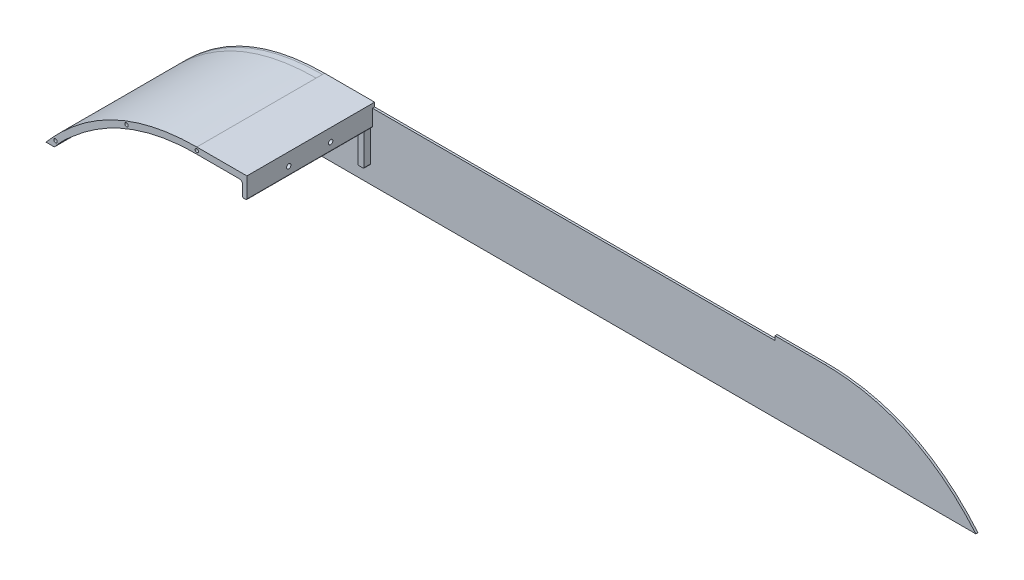
SolidWorks part; units mm, degrees
ref_plane "Front Plane" through (0, 0, 0) normal (0, 0, 1) x (1, 0, 0)
ref_plane "Top Plane" through (0, 0, 0) normal (0, 1, 0) x (1, 0, 0)
ref_plane "Right Plane" through (0, 0, 0) normal (1, 0, 0) x (0, 0, -1)
sketch "Sketch1" plane through (0, 0, 0) normal (0, 0, 1) x (1, 0, 0)
  line L0 (0, 0) -> (-304.8, 0)
  line L1 (0, 0) -> (609.6, 0)
  line L2 (0, 0) -> (0, 107.95) construction
  line L3 (0, 107.95) -> (609.6, 107.95)
  line L4 (609.6, 0) -> (609.6, 107.95) construction
  line L5 (609.6, 0) -> (914.4, 0)
  line L6 (304.8, -1000) -> (304.8, 49000) construction
  line L7 (0, 107.95) -> (-76.2, 107.95)
  line L8 (609.6, 107.95) -> (685.8, 107.95)
  spline S0 degree 2 poles (-304.8, 0) (-213.404, 107.36) (-76.2, 107.95) knots 0 0 0 1 1 1
  spline S1 degree 2 poles (914.4, 0) (823.004, 107.36) (685.8, 107.95) knots 0 0 0 1 1 1
  point P11 (304.8, 0)
  dimension "D1" = 609.6
  dimension "D2" = 107.95
  dimension "D3" = 304.8
  dimension "D4" = 76.2
extrude "Boss-Extrude1" add sketch "Sketch1" along normal blind 3.175
sketch "Sketch2" plane through (0, 0, 3.175) normal (0, 0, 1) x (1, 0, 0)
  line L8 (685.8, 107.95) -> (-76.2, 107.95) construction
  line L11 (0, 107.95) -> (609.6, 107.95)
  line L12 (0, 107.95) -> (0, 101.6) construction
  line L13 (0, 101.6) -> (609.6, 101.6)
  line L14 (609.6, 107.95) -> (609.6, 101.6) construction
  line L15 (-0.254, 107.95) -> (-0.254, 101.6)
  line L16 (609.854, 107.95) -> (609.854, 101.6)
  line L19 (609.6, 107.95) -> (609.854, 107.95)
  line L20 (609.6, 101.6) -> (609.854, 101.6)
  line L21 (-0.254, 107.95) -> (0, 107.95)
  line L22 (-0.254, 101.6) -> (0, 101.6)
  dimension "D1" = 609.6
  dimension "D2" = 6.35
  dimension "D3" = 0.254
  dimension "D4" = 0.254
extrude "Cut-Extrude1" cut sketch "Sketch2" against normal through all
sketch "Sketch3" plane through (0, 0, 3.175) normal (0, 0, 1) x (1, 0, 0)
  line L5 (-76.0908, 82.5502) -> (-76.2, 107.95) construction
  line L6 (685.8, 107.95) -> (609.854, 107.95)
  line L7 (609.854, 107.95) -> (609.854, 101.6)
  line L8 (609.854, 101.6) -> (-0.254, 101.6)
  line L9 (-0.254, 101.6) -> (-0.254, 107.95)
  line L10 (-0.254, 107.95) -> (-76.2, 107.95)
  line L11 (-304.8, 0) -> (914.4, 0)
  line L19 (-304.8, 0) -> (-254.508, 0)
  line L20 (-304.8, 0) -> (914.4, 0) construction
  line L21 (-254.508, 0) -> (-254.508, 15.3448)
  line L22 (-76.2, 107.95) -> (-0.254, 107.95)
  line L23 (-0.254, 107.95) -> (-0.254, 76.2)
  line L24 (-0.254, 76.2) -> (-6.604, 76.2)
  line L25 (-6.604, 76.2) -> (-6.604, 82.5502)
  line L26 (-6.604, 82.5502) -> (-76.0908, 82.5502)
  parabola Q2 (-76.2, 107.95) -> (-304.8, 0) focus (-138.8032, -41.5009) apex (-192.9562, 84.7198)
  parabola Q3 (914.4, 0) -> (685.8, 107.95) focus (748.4032, -41.5009) apex (802.5562, 84.7198)
  parabola Q4 (-76.2, 107.95) -> (-304.8, 0) focus (-138.8032, -41.5009) apex (-192.9562, 84.7198)
  spline S0 degree 1 poles (-76.0908, 82.5502) (-285.4592, -16.4649) knots 0 0 1 1 construction
  spline S1 degree 3 poles (-76.0908, 82.5502) (-78.7263, 82.5389) (-84.0207, 82.4515) (-94.414, 82.0204) (-107.175, 81.0024) (-122.0857, 79.0209) (-140.2937, 75.5918) (-157.8592, 70.8643) (-175.9104, 64.4537) (-194.5198, 56.4637) (-212.4049, 46.7322) (-228.6865, 35.996) (-240.414, 27.3) (-249.9299, 19.4397) (-257.5609, 12.6326) (-263.3873, 7.1473) (-268.2089, 2.3627) (-271.8925, -1.4301) (-275.5622, -5.3024) (-280.0978, -10.2646) (-283.6939, -14.3913) (-285.4592, -16.4649) knots 0.497516 0.497516 0.497516 0.497516 0.497684 0.497853 0.498189 0.498526 0.498863 0.499456 0.499793 0.50021 0.500884 0.501221 0.501558 0.501878 0.502046 0.502231 0.502399 0.502483 0.502568 0.502737 0.502905 0.502905 0.502905 0.502905 only from (-76.0908, 82.5502) to (-270.5007, 0) construction
  spline S2 degree 2 poles (-254.508, 15.3448) (-177.7983, 82.8932) (-76.0908, 82.5502) knots 0 0 0 1 1 1
  dimension "D2" = 31.75
  dimension "D3" = 6.35
  dimension "D5" = 50.292
  dimension "D1" = 0
  dimension "D4" = 25.4
extrude "Boss-Extrude2" add sketch "Sketch3" along normal blind 9.525
sketch "Sketch5" plane through (0, 0, 12.7) normal (0, 0, 1) x (1, 0, 0)
  line L7 (-304.8, 0) -> (-292.1, 0)
  line L8 (-76.0372, 98.4251) -> (-6.604, 98.4251)
  line L9 (-6.604, 98.4251) -> (-6.604, 82.5502)
  line L14 (-304.8, 0) -> (-254.508, 0)
  line L15 (-254.508, 0) -> (-254.508, 15.3448)
  line L16 (-76.0908, 82.5502) -> (-6.604, 82.5502)
  line L17 (-6.604, 82.5502) -> (-6.604, 76.2)
  line L18 (-6.604, 76.2) -> (-0.254, 76.2)
  line L19 (-0.254, 76.2) -> (-0.254, 107.95)
  line L20 (-0.254, 107.95) -> (-76.2, 107.95)
  line L24 (-6.604, 82.5502) -> (-6.604, 76.2)
  line L25 (-6.604, 76.2) -> (-0.254, 76.2)
  line L26 (-0.254, 76.2) -> (-0.254, 107.95)
  line L27 (-0.254, 107.95) -> (-76.2, 107.95)
  parabola Q4 (-76.2, 107.95) -> (-304.8, 0) focus (-138.8032, -41.5009) apex (-192.9562, 84.7198)
  parabola Q5 (-254.508, 15.3448) -> (-76.0908, 82.5502) focus (-126.3995, -51.2914) apex (-169.7975, 66.5726)
  parabola Q6 (-76.2, 107.95) -> (-304.8, 0) focus (-138.8032, -41.5009) apex (-192.9562, 84.7198)
  parabola Q7 (-254.508, 15.3448) -> (-76.0908, 82.5502) focus (-126.3995, -51.2914) apex (-169.7975, 66.5726) construction
  spline S0 degree 1 poles (-264.9993, 27.259) (-76.0372, 98.4251) knots 0 0 1 1 construction
  spline S1 degree 3 poles (-264.9993, 27.259) (-263.3249, 28.7335) (-259.9376, 31.6547) (-253.107, 37.2998) (-244.419, 44.0244) (-233.7687, 51.5472) (-219.2659, 60.8476) (-200.5783, 71.0931) (-177.2837, 81.1523) (-153.1553, 88.9561) (-132.3866, 93.5719) (-115.3933, 96.1333) (-102.4647, 97.4901) (-91.5371, 98.1519) (-82.7134, 98.4012) (-78.2591, 98.4326) (-76.0372, 98.4251) knots 0.497832 0.497832 0.497832 0.497832 0.497965 0.498098 0.498363 0.498629 0.498895 0.499427 0.499958 0.50049 0.501022 0.501287 0.501553 0.501819 0.501952 0.502085 0.502085 0.502085 0.502085
  spline S2 degree 2 poles (-264.9993, 27.259) (-280.0432, 15.0907) (-292.1, 0) knots 0 0 0 1 1 1
  dimension "D3" = 12.7
  dimension "D1" = 0
  dimension "D2" = 15.875
extrude "Boss-Extrude3" add sketch "Sketch5" along normal blind 180.975
sketch "Sketch6" plane through (0, 0, 12.7) normal (0, 0, 1) x (1, 0, 0)
  line L1 (-254.508, 0) -> (-226.4253, 0)
  line L2 (-254.508, 0) -> (-254.508, 28.575)
  line L3 (-254.508, 28.575) -> (-226.4253, 28.575)
  line L4 (-226.4253, 0) -> (-226.4253, 28.575)
  dimension "D1" = 28.575
extrude "Cut-Extrude2" cut sketch "Sketch6" against normal up to surface (9.525 mm away) up to face at (204.1979, 60.3971, 3.175)
sketch "Sketch7" plane through (0, 0, 12.7) normal (0, 0, 1) x (1, 0, 0)
  line L0 (-292.1, 0) -> (-254.508, 0) construction
  line L1 (-254.508, 0) -> (-254.508, 28.575) construction
  line L2 (-76.0651, 90.1702) -> (-9.6958, 90.1702) construction
  line L3 (-6.604, 98.4251) -> (-6.604, 76.2) construction
  circle A0 centre (-267.208, 10.16) radius 3.275
  circle A1 centre (-175.3658, 72.6223) radius 3.275
  circle A3 centre (-57.404, 90.1702) radius 3.275
  parabola Q0 (-238.3942, 28.575) -> (-76.0908, 82.5502) focus (-126.3995, -51.2914) apex (-169.7975, 66.5726) construction
  parabola Q1 (-238.3942, 28.575) -> (-76.0908, 82.5502) focus (-126.3995, -51.2914) apex (-169.7975, 66.5726) construction
  spline S0 degree 1 poles (-243.0182, 34.6317) (-76.0651, 90.1702) knots 0 0 1 1 construction
  spline S1 degree 3 poles (-243.0182, 34.6317) (-239.9935, 36.9409) (-233.8311, 41.4586) (-224.4638, 47.7679) (-214.9157, 53.6525) (-202.0674, 60.8581) (-190.551, 66.4075) (-178.8009, 71.3309) (-171.8366, 73.9914) (-159.5844, 78.2202) (-143.5556, 82.8056) (-125.3458, 86.3973) (-110.4698, 88.391) (-99.1613, 89.4468) (-89.6088, 89.961) (-81.8979, 90.1535) (-78.0064, 90.1767) (-76.0651, 90.1702) knots 0.498271 0.498271 0.498271 0.498271 0.49851 0.498748 0.498986 0.499225 0.499694 0.499813 0.500051 0.500178 0.500655 0.501131 0.50137 0.501608 0.501846 0.501966 0.502085 0.502085 0.502085 0.502085 construction
  dimension "D1" = 6.55
  dimension "D5" = 6.55
  dimension "D6" = 6.55
  dimension "D2" = 10.16
  dimension "D4" = 12.7
  dimension "D7" = 50.8
  dimension "D3" = 7.62
extrude "Cut-Extrude3" cut sketch "Sketch7" against normal through all
sketch "Sketch8" plane through (-0.254, 0, 0) normal (1, 0, 0) x (0, 0, -1)
  line L0 (-1151.3542, 88.9) -> (48848.6458, 88.9) construction
  line L1 (-193.675, 76.2) -> (-3.175, 76.2) construction
  line L2 (-3.175, 76.2) -> (-3.175, 101.6) construction
  circle A2 centre (-66.675, 88.9) radius 3.325
  circle A5 centre (-130.175, 88.9) radius 3.325
  dimension "D2" = 6.65
  dimension "D4" = 63.5
  dimension "D1" = 12.7
  dimension "D3" = 2
extrude "Cut-Extrude5" cut sketch "Sketch8" against normal up to surface (6.35 mm away) up to face at (-6.604, 85.7251, 69.85)
sketch "Sketch9" plane through (0, 0, 193.675) normal (0, 0, 1) x (1, 0, 0)
  circle A0 centre (-290.3708, 9.1426) radius 2.6
  circle A1 centre (-182.7594, 83.8165) radius 2.6
  circle A2 centre (-76.1798, 103.25) radius 2.6
  parabola Q0 (-76.2, 107.95) -> (-304.8, 0) focus (-138.8032, -41.5009) apex (-192.9562, 84.7198) construction
  parabola Q1 (-76.2, 107.95) -> (-304.8, 0) focus (-138.8032, -41.5009) apex (-192.9562, 84.7198) construction
  spline S0 degree 1 poles (-76.1798, 103.25) (-301.2212, -3.0467) knots 0 0 1 1 construction
  spline S1 degree 3 poles (-76.1798, 103.25) (-78.9851, 103.238) (-84.6167, 103.1451) (-95.7036, 102.6853) (-109.3519, 101.5971) (-125.3575, 99.4709) (-145.1456, 95.7451) (-161.7727, 91.2541) (-177.9517, 85.7316) (-188.5878, 81.5829) (-206.0869, 73.7491) (-227.5653, 62.0602) (-249.2337, 46.8941) (-265.8815, 33.1047) (-277.7275, 22.2059) (-286.3, 13.5161) (-292.1052, 7.2837) (-296.2196, 2.7435) (-299.3516, -0.8505) (-301.2212, -3.0467) knots 0.497516 0.497516 0.497516 0.497516 0.497684 0.497853 0.498189 0.498526 0.498863 0.499468 0.499636 0.499973 0.50021 0.500884 0.501558 0.501895 0.502231 0.502544 0.502628 0.502737 0.502905 0.502905 0.502905 0.502905 construction
  dimension "D2" = 5.2
  dimension "D3" = 5.2
  dimension "D4" = 5.2
  dimension "D1" = 4.7
extrude "Cut-Extrude6" cut sketch "Sketch9" against normal blind 12.7
sketch "Sketch11" plane through (-254.508, 0, 0) normal (1, 0, 0) x (0, 0, -1)
  line L0 (-3.175, 0) -> (-3.175, 28.575) construction
  line L1 (-12.7, 0) -> (-3.175, 0) construction
  circle A0 centre (-7.1374, 3.9751) radius 1.9
  circle A3 centre (-7.1374, 21.4251) radius 1.9
  dimension "D3" = 3.8
  dimension "D1" = 3.9624
  dimension "D2" = 3.9751
  dimension "D4" = 2
extrude "Boss-Extrude5" add sketch "Sketch11" along normal blind 10.16
sketch "Sketch14" plane through (0, 82.5502, 0) normal (0, -1, 0) x (1, 0, 0)
  line L5 (-76.0372, 12.7) -> (-6.604, 12.7) construction
  line L6 (-0.254, 3.175) -> (-12.954, 3.175)
  line L7 (-0.254, 3.175) -> (-0.254, 12.7)
  line L8 (-0.254, 12.7) -> (-12.954, 12.7)
  line L9 (-12.954, 3.175) -> (-12.954, 12.7)
  dimension "D1" = 12.7
extrude "Boss-Extrude8" add sketch "Sketch14" along normal offset from surface (57.1502 mm away) 25.4 up to face at (-48.3616, 0, 43.4975)
sketch "Sketch17" plane through (-0.254, 0, 0) normal (1, 0, 0) x (0, 0, -1)
  line L1 (-12.7, 76.2) -> (-3.175, 76.2)
  line L2 (-12.7, 76.2) -> (-12.7, 25.4)
  line L3 (-12.7, 25.4) -> (-3.175, 25.4)
  line L4 (-3.175, 76.2) -> (-3.175, 25.4)
extrude "Cut-Extrude9" cut sketch "Sketch17" against normal blind 3.175
fillet "Fillet1" radius 5 1 edges at (-6.604, 98.4251, 103.1875)
fillet "Fillet2" radius 2 2 edges at (-238.3942, 28.575, 7.9375) (-254.508, 28.575, 7.9375)
fillet "Fillet3" radius 1 1 edges at (-292.1, 0, 103.1875)
fillet "Fillet8" radius 5 1 edges at (-12.954, 82.5502, 7.9375)
fillet "Fillet9" radius 1.5 4 edges at (-0.254, 76.2, 98.425) (-6.604, 76.2, 103.1875) (-12.954, 25.4, 7.9375) (-3.429, 25.4, 7.9375)
fillet "Fillet10" radius 1.5 1 edges at (-3.429, 76.2, 7.9375)
sketch "Sketch18" plane through (0, 0, 0) normal (0, 0, -1) x (-1, 0, 0)
  line L0 (-1533.9053, 12.7) -> (48466.0947, 12.7) construction
  line L1 (304.8, 0) -> (-914.4, 0) construction
  circle A0 centre (114.3, 12.7) radius 3.275
  dimension "D2" = 6.55
  dimension "D1" = 12.7
  dimension "D3" = 114.3
extrude "Cut-Extrude10" cut sketch "Sketch18" against normal blind 12.7
